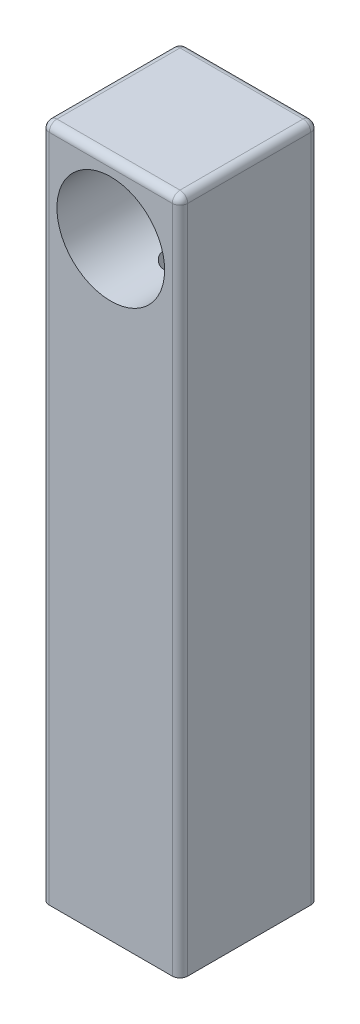
SolidWorks part; units mm, degrees
material "Teak"
ref_plane "Front Plane" through (0, 0, 0) normal (0, 0, 1) x (1, 0, 0)
ref_plane "Top Plane" through (0, 0, 0) normal (0, 1, 0) x (1, 0, 0)
ref_plane "Right Plane" through (0, 0, 0) normal (1, 0, 0) x (0, 0, -1)
sketch "Sketch1" plane through (0, 0, 0) normal (0, 1, 0) x (1, 0, 0)
  line L0 (1.143, 27.5046) -> (1.143, -29.6454) construction
  line L1 (-24.257, 27.5046) -> (26.543, 27.5046)
  line L2 (-27.432, 24.3296) -> (-27.432, -26.4704)
  line L3 (-24.257, -29.6454) -> (26.543, -29.6454)
  line L4 (29.718, 24.3296) -> (29.718, -26.4704)
  line L5 (-27.432, -1.0704) -> (29.718, -1.0704) construction
  arc A0 (-27.432, -26.4704) -> (-24.257, -29.6454) centre (-24.257, -26.4704) ccw
  arc A1 (26.543, -29.6454) -> (29.718, -26.4704) centre (26.543, -26.4704) ccw
  arc A2 (26.543, 27.5046) -> (29.718, 24.3296) centre (26.543, 24.3296) cw
  arc A3 (-24.257, 27.5046) -> (-27.432, 24.3296) centre (-24.257, 24.3296) ccw
  circle A4 centre (-13.1445, 13.2171) radius 4.9606
  circle A5 centre (15.4305, 13.2171) radius 4.9606
  circle A6 centre (15.4305, -15.3579) radius 4.9606
  circle A7 centre (-13.1445, -15.3579) radius 4.9606
  circle A8 centre (1.143, -1.0704) radius 6.35
  point P6 (-27.432, -29.6454)
  point P11 (29.718, 27.5046)
  point P14 (-27.432, 27.5046)
  dimension "D3" = 3.175
  dimension "D12" = 9.9212
  dimension "D13" = 9.9212
  dimension "D14" = 9.9212
  dimension "D15" = 9.9212
  dimension "D1" = 57.15
  dimension "D2" = 57.15
  dimension "D4" = 14.2875
  dimension "D5" = 14.2875
  dimension "D6" = 14.2875
  dimension "D7" = 14.2875
  dimension "D8" = 14.2875
  dimension "D9" = 14.2875
  dimension "D10" = 14.2875
  dimension "D11" = 14.2875
extrude "Boss-Extrude1" add sketch "Sketch1" along normal blind 279.4 contours L2 A0 L3 A1 L4 A2 L1 A3
extrude "Cut-Extrude1" cut sketch "Sketch1<4>" along normal blind 25.4 contours A7 | A6 | A4 | A5
sketch "Sketch1<4>" plane through (0, 0, 0) normal (0, 1, 0) x (1, 0, 0) same geometry as "Sketch1"
extrude "Cut-Extrude2" cut sketch "Sketch1<5>" along normal blind 250.825 contours A8
sketch "Sketch1<5>" plane through (0, 0, 0) normal (0, 1, 0) x (1, 0, 0) same geometry as "Sketch1"
fillet "Fillet1" radius 3.175 8 edges at (28.7881, 279.4, -26.5746) (1.143, 279.4, -27.5046) (-26.5021, 279.4, -26.5746) (-27.432, 279.4, 1.0704) (-26.5021, 279.4, 28.7155) (1.143, 279.4, 29.6454) (28.7881, 279.4, 28.7155) (29.718, 279.4, 1.0704)
ref_plane "Plane1" through (0, 0, 29.6454) normal (0, 0, 1) x (1, 0, 0)
sketch "Sketch4" plane through (0, 0, 29.6454) normal (0, 0, 1) x (1, 0, 0)
  line L0 (29.718, 250.825) -> (-27.432, 250.825)
  line L1 (-27.432, 276.225) -> (-27.432, 0) construction
  line L3 (29.718, 276.225) -> (29.718, 0) construction
  line L5 (-24.257, 279.4) -> (26.543, 279.4) construction
  circle A0 centre (1.143, 250.825) radius 22.225
  point P0 (0, 0)
  point P5 (1.143, 250.825)
  dimension "D1" = 28.575
  dimension "D2" = 28.575
  dimension "D3" = 28.575
other "AlignGroup1"
extrude "Cut-Extrude3" cut sketch "Sketch4" against normal blind 44.45 contours A0
